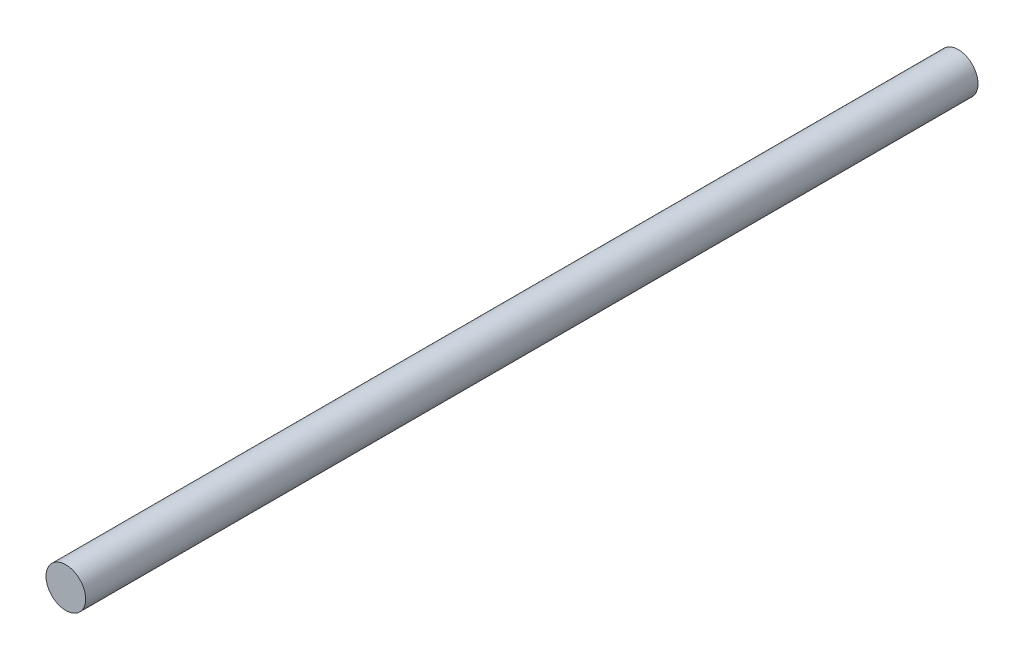
SolidWorks part; units mm, degrees
ref_plane "Front Plane" through (0, 0, 0) normal (0, 0, 1) x (1, 0, 0)
ref_plane "Top Plane" through (0, 0, 0) normal (0, 1, 0) x (1, 0, 0)
ref_plane "Right Plane" through (0, 0, 0) normal (1, 0, 0) x (0, 0, -1)
sketch "Sketch1" plane through (0, 0, 0) normal (0, 0, 1) x (1, 0, 0)
  circle A0 centre (0, 0) radius 4
  dimension "D1" = 8
extrude "Boss-Extrude1" add sketch "Sketch1" along normal blind 180
